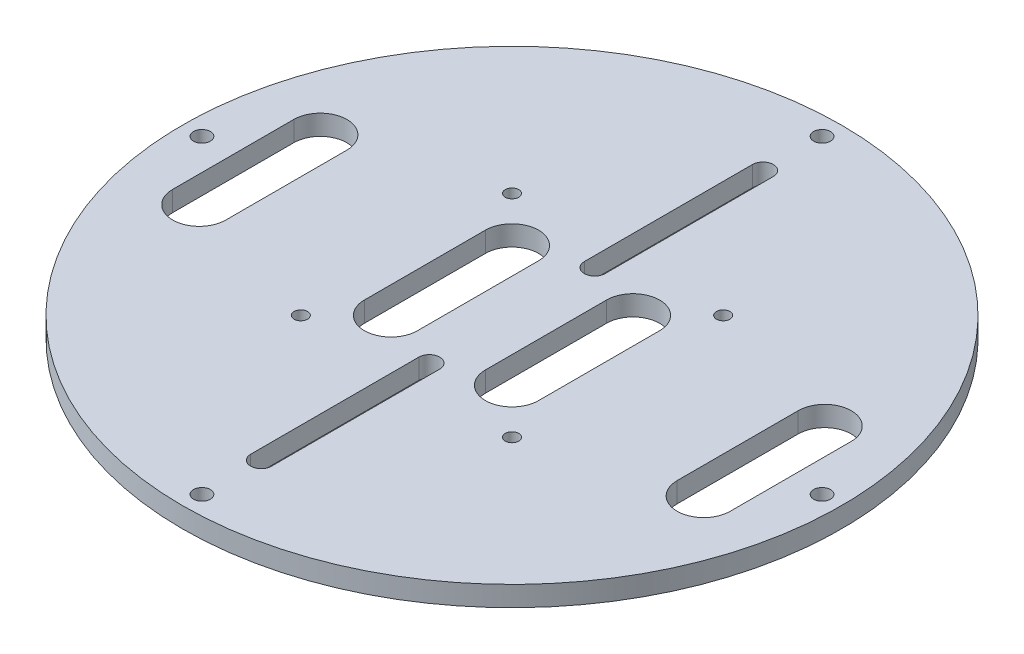
SolidWorks part; units mm, degrees
ref_plane "前视" through (0, 0, 0) normal (0, 0, 1) x (1, 0, 0)
ref_plane "上视" through (0, 0, 0) normal (0, 1, 0) x (1, 0, 0)
ref_plane "右视" through (0, 0, 0) normal (1, 0, 0) x (0, 0, -1)
sketch "草图1" plane through (0, 0, 0) normal (0, 1, 0) x (1, 0, 0)
  circle A0 centre (0, 0) radius 49
  dimension "D1" = 98
extrude "凸台-拉伸1" add sketch "草图1" along normal blind 3
sketch "草图6" plane through (0, 3, 0) normal (0, 1, 0) x (1, 0, 0)
  line L0 (0, 12.3) -> (0, 37.3) construction
  line L1 (-1.55, 12.3) -> (-1.55, 37.3)
  line L2 (1.55, 12.3) -> (1.55, 37.3)
  arc A0 (-1.55, 12.3) -> (1.55, 12.3) centre (0, 12.3) ccw
  arc A1 (1.55, 37.3) -> (-1.55, 37.3) centre (0, 37.3) ccw
  point P3 (0, 24.8)
  dimension "D1" = 25
  dimension "D2" = 12.3
extrude "切除-拉伸1" cut sketch "草图6" against normal through all
pattern_circular "阵列(圆周)2" count 2 over 360 about axis through (0, 3, 0) along (0, -1, 0) of "切除-拉伸1"
sketch "草图7" plane through (0, 3, 0) normal (0, 1, 0) x (1, 0, 0)
  line L0 (-51.2516, 0) -> (52.7908, 0) construction
  line L1 (-17.8863, 15.7) -> (-13.3805, 15.7) construction
  line L2 (-15.7, 17.8338) -> (-15.7, 13.4893) construction
  dimension "D1" = 15.7
  dimension "D2" = 15.7
sketch "草图8" plane through (0, 3, 0) normal (0, 1, 0) x (1, 0, 0)
  line L0 (-17.8863, 15.7) -> (-13.3805, 15.7) construction
  circle A0 centre (-15.7, 15.7) radius 1
  dimension "D1" = 2
sketch "草图9" plane through (0, 3, 0) normal (0, 1, 0) x (1, 0, 0)
  line L0 (-9, 26.2025) -> (-9, -24.6699) construction
  line L1 (-9, -9) -> (-9, 9) construction
  line L2 (-12.95, -9) -> (-12.95, 9)
  line L3 (-5.05, -9) -> (-5.05, 9)
  line L4 (-51.2516, 0) -> (52.7908, 0) construction
  arc A0 (-12.95, -9) -> (-5.05, -9) centre (-9, -9) ccw
  arc A1 (-5.05, 9) -> (-12.95, 9) centre (-9, 9) ccw
  point P4 (-9, 0)
extrude "切除-拉伸3" cut sketch "草图9" against normal through all
pattern_linear "阵列(线性)1" count 2 spacing 28.5 along (-1, 0, 0) of "切除-拉伸3"
pattern_circular "阵列(圆周)5" count 2 over 360 about axis through (0, 3, 0) along (0, -1, 0) of "阵列(线性)1", "切除-拉伸3"
sketch "草图14" plane through (0, 3, 0) normal (0, 1, 0) x (1, 0, 0)
  line L0 (0, 54.6999) -> (0, -58.67) construction
  circle A0 centre (0, 46.1) radius 1.25
  dimension "D1" = 46.1
extrude "切除-拉伸4" cut sketch "草图14" against normal through all
pattern_circular "阵列(圆周)6" count 4 over 360 about axis through (0, 3, 0) along (0, -1, 0) of "切除-拉伸4"
sketch "草图15" plane through (0, 3, 0) normal (0, 1, 0) x (1, 0, 0)
  line L0 (5.1524, -24.8) -> (-5.5286, -24.8) construction
  line L1 (-51.2516, 0) -> (52.7908, 0) construction
  dimension "D1" = 24.8
sketch "草图16" plane through (0, 3, 0) normal (0, 1, 0) x (1, 0, 0)
  line L0 (0, 0) -> (-15.7936, 15.7936) construction
  line L1 (-15.7936, 15.7936) -> (-16.8429, 16.8429) construction
  line L2 (-51.2516, 0) -> (52.7908, 0) construction
  dimension "D1" = 45
extrude "切除-拉伸5" cut sketch "草图8" against normal through all
pattern_circular "阵列(圆周)7" count 4 over 360 about axis through (0, 3, 0) along (0, -1, 0) of "切除-拉伸5"
